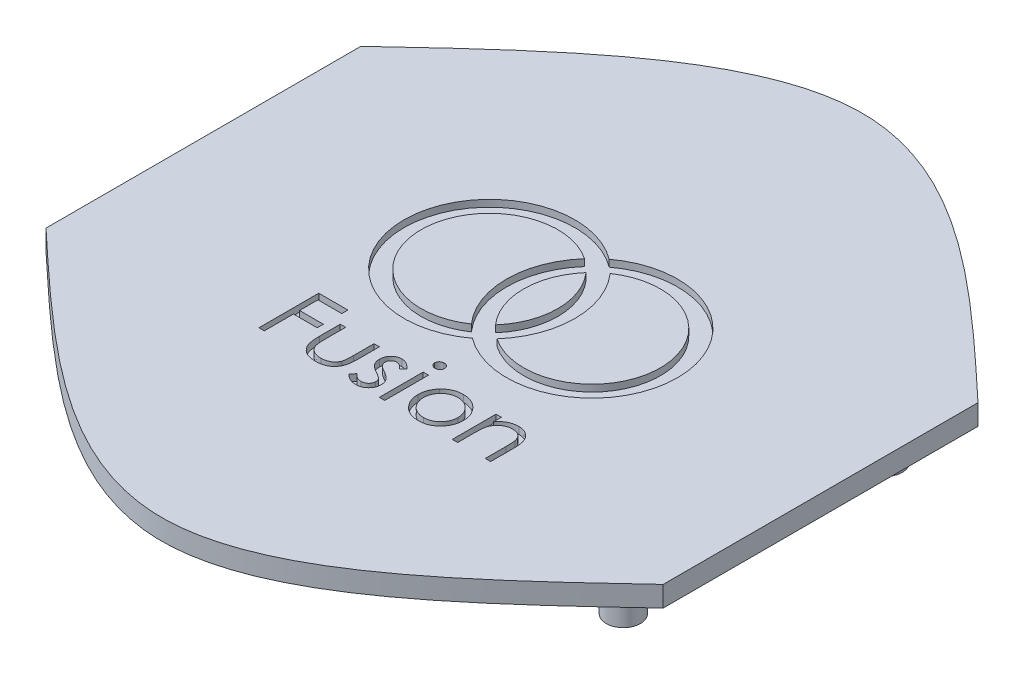
SolidWorks part; units mm, degrees
material "Stainless Steel (ferritic)"
ref_plane "Front Plane" through (0, 0, 0) normal (0, 0, 1) x (1, 0, 0)
ref_plane "Top Plane" through (0, 0, 0) normal (0, 1, 0) x (1, 0, 0)
ref_plane "Right Plane" through (0, 0, 0) normal (1, 0, 0) x (0, 0, -1)
sketch "Sketch1" plane through (0, 0, 0) normal (0, 1, 0) x (1, 0, 0)
  line L0 (0, 41.8633) -> (0, 60.2733)
  line L1 (-36.09, 51.0683) -> (0, 51.0683) construction
  line L2 (-36.09, 60.2733) -> (-36.09, 41.8633)
  spline S0 degree 3 poles (-36.09, 41.8633) (-30.075, 36.2248) (-18.045, 24.9481) (-6.015, 36.2248) (0, 41.8633) knots 0 0 0 0 0.5 1 1 1 1
  spline S1 degree 3 poles (-36.09, 60.2733) (-30.075, 65.9118) (-18.045, 77.1885) (-6.015, 65.9118) (0, 60.2733) knots 0 0 0 0 0.5 1 1 1 1
  dimension "D1" = 0
  dimension "D2" = 51.0683
extrude "Boss-Extrude1" add sketch "Sketch1" along normal blind 1.2
sketch "Sketch3" plane through (0, 0, 0) normal (0, -1, 0) x (1, 0, 0)
  line L0 (-34.09, -59.4065) -> (-34.09, -42.73) construction
  line L1 (-34.09, -42.73) -> (-28.8819, -38.0422) construction
  line L2 (-3.8794, -58.7225) -> (-5.4167, -60.0018) construction
  line L3 (-3.8794, -43.4141) -> (-2, -42.73) construction
  line L4 (-5.4167, -60.0018) -> (-4.1334, -61.5358) construction
  line L5 (-32.2106, -58.7225) -> (-30.6733, -60.0018) construction
  line L6 (-32.2106, -58.7225) -> (-32.2106, -43.4141) construction
  line L7 (-30.6733, -60.0018) -> (-31.9566, -61.5358) construction
  line L8 (-3.8794, -58.7225) -> (-2, -59.4065) construction
  line L9 (-31.9566, -61.5358) -> (-34.09, -59.4065) construction
  line L10 (-4.1334, -61.5358) -> (-2, -59.4065) construction
  line L11 (-28.8819, -38.0422) -> (-27.5986, -39.5762) construction
  line L13 (-2, -59.4065) -> (-34.09, -59.4065) construction
  line L14 (-18.045, -59.4065) -> (-18.045, -32.5864) construction
  line L15 (-32.2106, -58.7225) -> (-34.09, -59.4065) construction
  line L16 (-32.2106, -43.4141) -> (-34.09, -42.73) construction
  line L17 (-27.5986, -39.5762) -> (-32.2106, -43.4141) construction
  line L18 (-2, -42.73) -> (-7.2081, -38.0422) construction
  line L19 (-3.8794, -58.7225) -> (-3.8794, -43.4141) construction
  line L22 (-3.8794, -43.4141) -> (-8.4914, -39.5762) construction
  line L24 (-2, -59.4065) -> (-2, -42.73) construction
  line L25 (-8.4914, -39.5762) -> (-7.2081, -38.0422) construction
  circle A0 centre (-32.2106, -58.7225) radius 1
  circle A1 centre (-32.2106, -43.4141) radius 1
  circle A2 centre (-3.8794, -43.4141) radius 1
  circle A3 centre (-3.8794, -58.7225) radius 1
  dimension "D9" = 2
  dimension "D10" = 2
  dimension "D11" = 2
  dimension "D12" = 2
  dimension "D4" = 2
  dimension "D5" = 2
  dimension "D6" = 2
  dimension "D7" = 2
  dimension "D8" = 6
extrude "Boss-Extrude2" add sketch "Sketch3" along normal blind 3
sketch "Sketch5" plane through (0, 1.2, 0) normal (0, 1, 0) x (1, 0, 0)
  line L0 (0, 52.7511) -> (-36.09, 52.7511) construction
  line L3 (-18.045, 52.7511) -> (-18.045, 30.5864) construction
  line L4 (-18.045, 30.5864) -> (-18.045, 71.5501) construction
  line L5 (-6.8029, 66.3482) -> (-6.8029, 35.7883) construction
  line L6 (-27.9479, 67.3877) -> (-27.9479, 34.7488) construction
  line L7 (-35.8338, 60.5134) -> (-0.2561, 60.5134) construction
  line L8 (-34.9937, 43.2914) -> (-1.0963, 43.2914) construction
  circle A0 centre (-21.045, 52.7511) radius 4
  circle A1 centre (-15.045, 52.7511) radius 4
  circle A2 centre (-15.045, 52.7511) radius 5
  circle A3 centre (-21.045, 52.7511) radius 5
  spline S0 degree 3 poles (-36.09, 41.8633) (-30.075, 36.2248) (-18.045, 24.9481) (-6.015, 36.2248) (0, 41.8633) knots 0 0 0 0 0.5 1 1 1 1 construction
  spline S1 degree 3 poles (0, 60.2733) (-6.015, 65.9118) (-18.045, 77.1885) (-30.075, 65.9118) (-36.09, 60.2733) knots 0 0 0 0 0.5 1 1 1 1 construction
  text T1 "Fusion\r\n" font "Century Gothic" height 3.5
  dimension "D1" = 8
  dimension "D2" = 8
  dimension "D3" = 3
  dimension "D4" = 3
  dimension "D5" = 1
sketch "Sketch6" plane through (0, 1.2, 0) normal (0, 1, 0) x (1, 0, 0)
  line L0 (0, 54.1843) -> (-36.09, 54.1843) construction
  line L1 (-18.045, 54.1843) -> (-18.045, 32.0197) construction
  line L2 (-18.045, 32.0197) -> (-18.045, 72.9834) construction
  line L3 (-27.9892, 68.821) -> (-27.9892, 36.1821) construction
  line L4 (-35.0349, 43.0401) -> (-1.1376, 43.0401) construction
  line L5 (0, 41.8633) -> (0, 60.2733) construction
  line L6 (-36.09, 60.2733) -> (-36.09, 41.8633) construction
  text T0 "Fusion"
extrude "Cut-Extrude1" cut sketch "Sketch5" against normal blind 0.4 contours A3 A2 A1 | A2 A3 A1 A0 | A1 A3 A0 | A0 A2 A1 | A1 A3 A2 A0 | A2 A3 A0 region at (-16.9146, 1.2, -52.7511) region at (-19.1754, 1.2, -52.7511) region at (-18.045, 1.2, -56.0946) region at (-18.045, 1.2, -49.4076) region at (-25.1731, 1.2, -52.7511) region at (-17.5654, 1.2, -56.5179)
extrude "Cut-Extrude2" cut sketch "Sketch6" against normal blind 0.4
